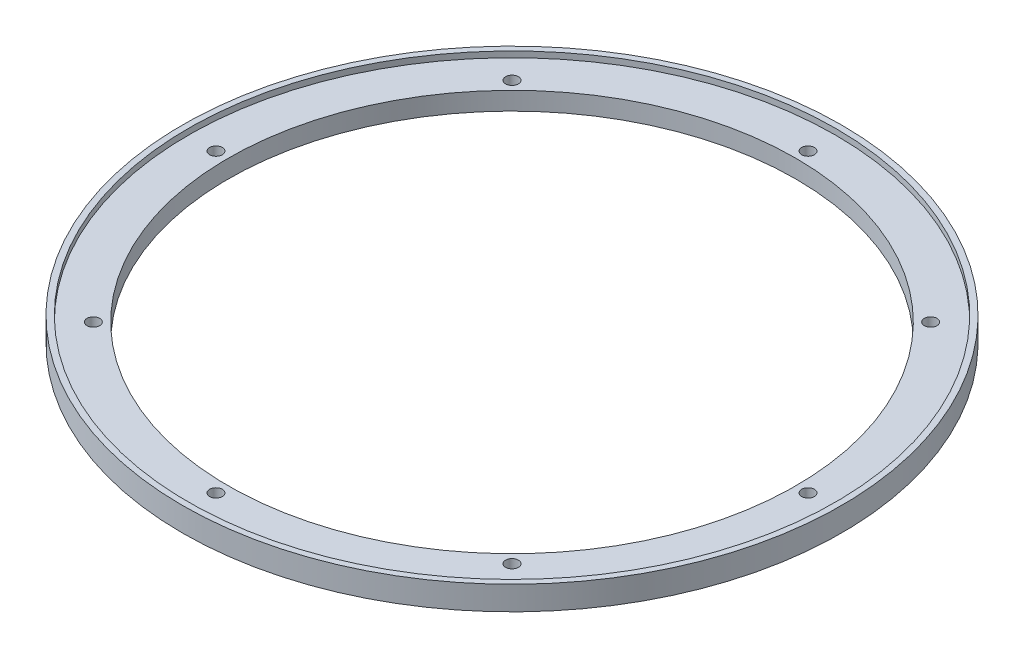
SolidWorks part; units mm, degrees
ref_plane "前视基准面" through (0, 0, 0) normal (0, 0, 1) x (1, 0, 0)
ref_plane "上视基准面" through (0, 0, 0) normal (0, 1, 0) x (1, 0, 0)
ref_plane "右视基准面" through (0, 0, 0) normal (1, 0, 0) x (0, 0, -1)
other "Configuration Table"
sketch "草图1" plane through (0, 0, 0) normal (0, 0, 1) x (1, 0, 0)
  line L0 (0, 0) -> (0, 17.2398) construction
  line L1 (111.6, 6.1) -> (111.6, 8.1)
  line L2 (96.1, 6.1) -> (109.6, 6.1)
  line L3 (96.1, 6.1) -> (96.1, 0)
  line L4 (96.1, 0) -> (111.6, 0)
  line L5 (111.6, 6.1) -> (111.6, 0)
  line L6 (111.6, 8.1) -> (109.6, 8.1)
  line L7 (109.6, 8.1) -> (109.6, 6.1)
  dimension "D1" = 6.1
  dimension "D2" = 13.5
  dimension "D3" = 96.1
  dimension "D4" = 2
  dimension "D5" = 2
revolve "旋转1" add sketch "草图1" angle 360 about L0
sketch "草图2" plane through (0, 6.1, 0) normal (0, 1, 0) x (1, 0, 0)
  circle A0 centre (0, 0) radius 100.25 construction
  circle A1 centre (-100.25, 0) radius 2.15
  circle A2 centre (-70.8875, 70.8875) radius 2.15
  circle A3 centre (0, 100.25) radius 2.15
  circle A4 centre (70.8875, 70.8875) radius 2.15
  circle A5 centre (100.25, 0) radius 2.15
  circle A6 centre (70.8875, -70.8875) radius 2.15
  circle A7 centre (0, -100.25) radius 2.15
  circle A8 centre (-70.8875, -70.8875) radius 2.15
  point P22 (0, 0)
  dimension "D1" = 200.5
  dimension "D2" = 4.3
  dimension "D3" = 8
extrude "切除-拉伸1" cut sketch "草图2" against normal up to next
